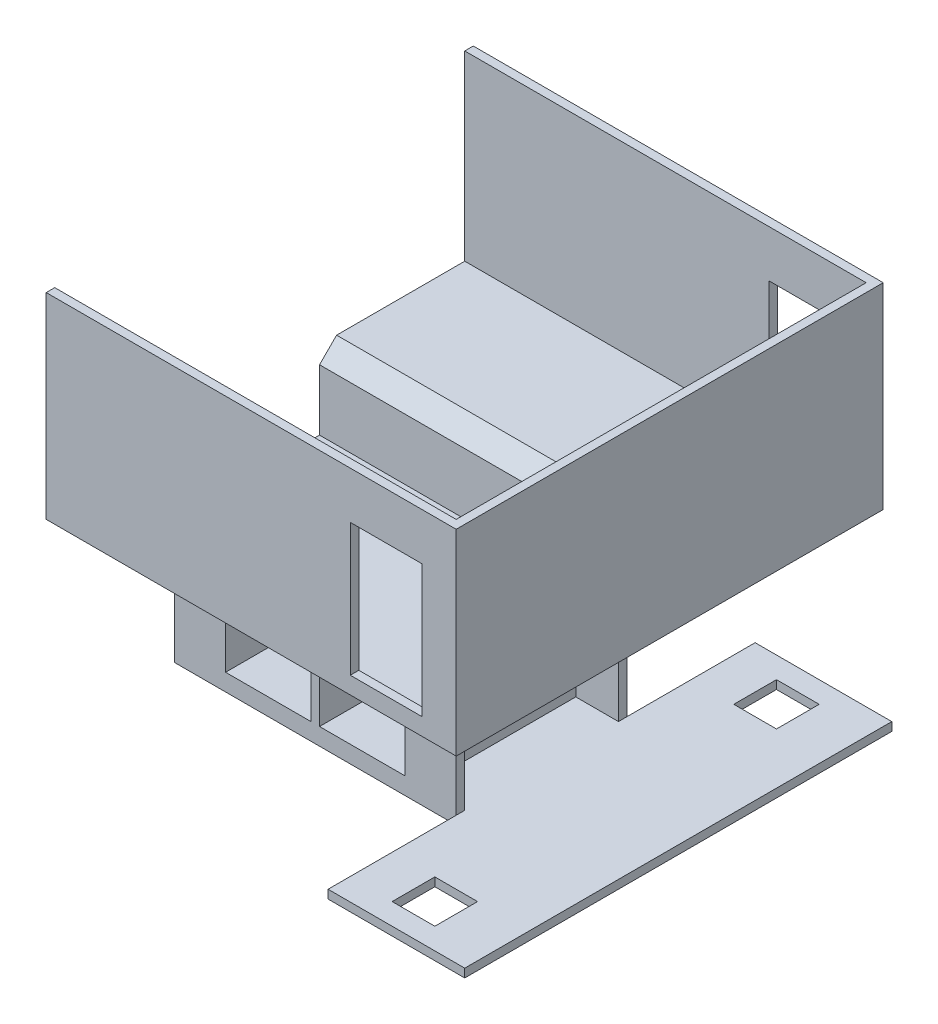
SolidWorks part; units mm, degrees
ref_plane "Front Plane" through (0, 0, 0) normal (0, 0, 1) x (1, 0, 0)
ref_plane "Top Plane" through (0, 0, 0) normal (0, 1, 0) x (1, 0, 0)
ref_plane "Right Plane" through (0, 0, 0) normal (1, 0, 0) x (0, 0, -1)
sketch "Sketch1" plane through (0, 0, 0) normal (0, 1, 0) x (1, 0, 0)
  line L1 (-23.6116, 30.0362) -> (21.3884, 30.0362)
  line L2 (-23.6116, 30.0362) -> (-23.6116, -19.9638)
  line L3 (-23.6116, -19.9638) -> (21.3884, -19.9638)
  line L4 (21.3884, 30.0362) -> (21.3884, -19.9638)
  dimension "D1" = 50
  dimension "D2" = 45
extrude "Boss-Extrude1" add sketch "Sketch1" along normal blind 45
sketch "Sketch2" plane through (0, 0, 19.9638) normal (0, 0, 1) x (1, 0, 0)
  line L1 (-23.6116, 0) -> (-1.6116, 0)
  line L2 (-23.6116, 0) -> (-23.6116, 22)
  line L3 (-23.6116, 22) -> (-1.6116, 22)
  line L4 (-1.6116, 0) -> (-1.6116, 22)
  dimension "D1" = 22
  dimension "D2" = 22
extrude "Cut-Extrude2" cut sketch "Sketch2" against normal blind 15
sketch "Sketch3" plane through (0, 0, 4.9638) normal (0, 0, 1) x (1, 0, 0)
  line L0 (-23.6116, 0) -> (-1.6116, 0) construction
  line L1 (-7.6116, 2) -> (-17.6116, 2)
  line L2 (-7.6116, 2) -> (-7.6116, 14)
  line L3 (-7.6116, 14) -> (-17.6116, 14)
  line L4 (-17.6116, 2) -> (-17.6116, 14)
  line L5 (-23.6116, 22) -> (-23.6116, 0) construction
  line L6 (-1.6116, 0) -> (-1.6116, 22) construction
  dimension "D1" = 10
  dimension "D2" = 12
  dimension "D3" = 2
  dimension "D4" = 6
  dimension "D5" = 6
extrude "Cut-Extrude3" cut sketch "Sketch3" against normal blind 70
sketch "Sketch4" plane through (0, 0, -30.0362) normal (0, 0, -1) x (-1, 0, 0)
  line L0 (7.6116, 2) -> (7.6116, 14) construction
  line L1 (6.6116, 2) -> (-3.3884, 2)
  line L2 (6.6116, 2) -> (6.6116, 14)
  line L3 (6.6116, 14) -> (-3.3884, 14)
  line L4 (-3.3884, 2) -> (-3.3884, 14)
  line L6 (-21.3884, 0) -> (23.6116, 0) construction
  dimension "D1" = 10
  dimension "D2" = 12
  dimension "D3" = 1
  dimension "D4" = 2
extrude "Cut-Extrude4" cut sketch "Sketch4" against normal blind 70
sketch "Sketch5" plane through (0, 0, -30.0362) normal (0, 0, -1) x (-1, 0, 0)
  line L0 (-21.3884, 0) -> (23.6116, 0) construction
  line L1 (-9.3884, 0) -> (12.6116, 0)
  line L2 (-9.3884, 0) -> (-9.3884, 22)
  line L3 (-9.3884, 22) -> (12.6116, 22)
  line L4 (12.6116, 0) -> (12.6116, 22)
  dimension "D1" = 22
  dimension "D2" = 22
  dimension "D3" = 6
  dimension "D4" = 6
extrude "Cut-Extrude5" cut sketch "Sketch5" against normal blind 15
sketch "Sketch6" plane through (-23.6116, 0, 0) normal (-1, 0, 0) x (0, 0, 1)
  line L1 (-30.0362, 0) -> (-15.0362, 0)
  line L2 (-30.0362, 0) -> (-30.0362, 21.8834)
  line L3 (-30.0362, 21.8834) -> (-15.0362, 21.8834)
  line L4 (-15.0362, 0) -> (-15.0362, 21.8834)
  dimension "D1" = 15
extrude "Cut-Extrude6" cut sketch "Sketch6" against normal blind 15
sketch "Sketch7" plane through (0, 0, 19.9638) normal (0, 0, 1) x (1, 0, 0)
  line L1 (-1.6116, 0) -> (3.3884, 0)
  line L2 (-1.6116, 0) -> (-1.6116, 22)
  line L3 (-1.6116, 22) -> (3.3884, 22)
  line L4 (3.3884, 0) -> (3.3884, 22)
  dimension "D1" = 22
extrude "Cut-Extrude7" cut sketch "Sketch7" against normal blind 15
sketch "Sketch8" plane through (-23.6116, 0, 0) normal (-1, 0, 0) x (0, 0, 1)
  line L0 (-30.0362, 45) -> (19.9638, 45) construction
  line L1 (-29.0362, 23.681) -> (18.9638, 23.681)
  line L2 (-29.0362, 23.681) -> (-29.0362, 45)
  line L3 (-29.0362, 45) -> (18.9638, 45)
  line L4 (18.9638, 23.681) -> (18.9638, 45)
  line L5 (-30.0362, 45) -> (-30.0362, 21.8834) construction
  line L6 (19.9638, 45) -> (19.9638, 22) construction
  dimension "D1" = 1
  dimension "D2" = 1
extrude "Cut-Extrude8" cut sketch "Sketch8" against normal blind 44
sketch "Sketch9" plane through (-12.6116, 0, 0) normal (1, 0, 0) x (0, 0, -1)
  line L1 (30.0362, 21.8834) -> (15.0362, 21.8834)
  line L2 (30.0362, 21.8834) -> (30.0362, 22)
  line L3 (30.0362, 22) -> (15.0362, 22)
  line L4 (15.0362, 21.8834) -> (15.0362, 22)
extrude "Cut-Extrude9" cut sketch "Sketch9" against normal blind 44
sketch "Sketch10" plane through (-23.6116, 0, 0) normal (-1, 0, 0) x (0, 0, 1)
  line L0 (-29.0362, 23.681) -> (18.9638, 23.681) construction
  line L1 (-14.0362, 14.5456) -> (3.9638, 14.5456)
  line L2 (-14.0362, 14.5456) -> (-14.0362, 23.681)
  line L3 (-14.0362, 23.681) -> (3.9638, 23.681)
  line L4 (3.9638, 14.5456) -> (3.9638, 23.681)
  line L5 (-15.0362, 0) -> (-15.0362, 22) construction
  line L6 (4.9638, 22) -> (4.9638, 0) construction
  dimension "D1" = 1
  dimension "D2" = 1
extrude "Cut-Extrude10" cut sketch "Sketch10" against normal blind 44
sketch "Sketch11" plane through (0, 0, -30.0362) normal (0, 0, -1) x (-1, 0, 0)
  line L1 (-9.3884, 0) -> (-21.3884, 0)
  line L2 (-9.3884, 0) -> (-9.3884, 45)
  line L3 (-9.3884, 45) -> (-21.3884, 45)
  line L4 (-21.3884, 0) -> (-21.3884, 45)
extrude "Cut-Extrude11" cut sketch "Sketch11" against normal blind 50
sketch "Sketch12" plane through (9.3884, 0, 0) normal (1, 0, 0) x (0, 0, -1)
  line L0 (-3.9638, 23.681) -> (-3.9638, 14.5456) construction
  line L1 (-19.9638, 0) -> (-4.9638, 0)
  line L2 (-19.9638, 0) -> (-19.9638, 22)
  line L3 (-19.9638, 22) -> (-4.9638, 22)
  line L4 (-4.9638, 0) -> (-4.9638, 22)
  dimension "D1" = 1
  dimension "D2" = 0
extrude "Cut-Extrude12" cut sketch "Sketch12" against normal blind 10
sketch "Sketch14" plane through (9.3884, 0, 0) normal (1, 0, 0) x (0, 0, -1)
  line L0 (-4.9638, 0) -> (15.0362, 0) construction
  line L1 (-3.9638, 14.5456) -> (14.0362, 14.5456)
  line L2 (-3.9638, 14.5456) -> (-3.9638, 1)
  line L3 (-3.9638, 1) -> (14.0362, 1)
  line L4 (14.0362, 14.5456) -> (14.0362, 1)
  line L5 (14.0362, 14.5456) -> (14.0362, 23.681) construction
  dimension "D1" = 1
  dimension "D2" = 0
extrude "Cut-Extrude17" cut sketch "Sketch14" against normal blind 5
sketch "Sketch16" plane through (0, 0, 0) normal (0, -1, 0) x (-1, 0, 0)
  line L2 (-9.3884, -4.9638) -> (-9.3884, 30.0362)
  line L3 (-9.3884, 30.0362) -> (-25.286, 30.0362)
  line L4 (-25.286, -1.1069) -> (-25.286, 30.0362)
  line L6 (-9.3884, -4.9638) -> (-9.3884, -19.9638)
  line L7 (-9.3884, -19.9638) -> (-25.286, -19.9638)
  line L8 (-25.286, -1.1069) -> (-25.286, -19.9638)
  dimension "D1" = 50
  dimension "D2" = 0
extrude "Boss-Extrude2" add sketch "Sketch16" against normal blind 1
sketch "Sketch18" plane through (0, 1, 0) normal (0, 1, 0) x (1, 0, 0)
  line L1 (9.3884, -19.9638) -> (25.3884, -19.9638)
  line L2 (9.3884, -19.9638) -> (9.3884, 30.0362)
  line L3 (9.3884, 30.0362) -> (25.3884, 30.0362)
  line L4 (25.3884, -19.9638) -> (25.3884, 30.0362)
  dimension "D1" = 16
extrude "Boss-Extrude3" add sketch "Sketch18" against normal blind 1
sketch "Sketch19" plane through (0, 1, 0) normal (0, 1, 0) x (1, 0, 0)
  line L0 (25.3884, -19.9638) -> (9.3884, -19.9638) construction
  line L1 (14.3884, -17.4638) -> (19.3884, -17.4638)
  line L2 (14.3884, -17.4638) -> (14.3884, -12.4638)
  line L3 (14.3884, -12.4638) -> (19.3884, -12.4638)
  line L4 (19.3884, -17.4638) -> (19.3884, -12.4638)
  line L5 (14.3884, 22.5362) -> (19.3884, 22.5362)
  line L6 (14.3884, 22.5362) -> (14.3884, 27.5362)
  line L7 (14.3884, 27.5362) -> (19.3884, 27.5362)
  line L8 (19.3884, 22.5362) -> (19.3884, 27.5362)
  line L9 (9.3884, 30.0362) -> (25.3884, 30.0362) construction
  line L10 (9.3884, -19.9638) -> (9.3884, -4.9638) construction
  line L11 (9.3884, 15.0362) -> (9.3884, 30.0362) construction
  dimension "D1" = 5
  dimension "D2" = 5
  dimension "D3" = 5
  dimension "D4" = 2.5
  dimension "D5" = 2.5
  dimension "D6" = 5
  dimension "D7" = 5
extrude "Cut-Extrude18" cut sketch "Sketch19" against normal blind 1
sketch "Sketch21" plane through (9.3884, 0, 0) normal (1, 0, 0) x (0, 0, -1)
  line L1 (-19.9638, 22) -> (30.0362, 22)
  line L2 (-19.9638, 22) -> (-19.9638, 45)
  line L3 (-19.9638, 45) -> (30.0362, 45)
  line L4 (30.0362, 22) -> (30.0362, 45)
extrude "Boss-Extrude4" add sketch "Sketch21" along normal blind 15
sketch "Sketch22" plane through (0, 0, 19.9638) normal (0, 0, 1) x (1, 0, 0)
  line L0 (24.3884, 22) -> (-23.6116, 22) construction
  line L1 (20.3884, 39.5) -> (11.9884, 39.5)
  line L2 (20.3884, 39.5) -> (20.3884, 24)
  line L3 (20.3884, 24) -> (11.9884, 24)
  line L4 (11.9884, 39.5) -> (11.9884, 24)
  line L5 (24.3884, 45) -> (24.3884, 22) construction
  dimension "D1" = 8.4
  dimension "D2" = 15.5
  dimension "D3" = 2
  dimension "D4" = 4
extrude "Cut-Extrude21" cut sketch "Sketch22" against normal blind 90
sketch "Sketch24" plane through (9.3884, 0, 0) normal (-1, 0, 0) x (0, 0, 1)
  line L1 (-29.0362, 23.681) -> (18.9638, 23.681)
  line L2 (-29.0362, 23.681) -> (-29.0362, 45)
  line L3 (-29.0362, 45) -> (18.9638, 45)
  line L4 (18.9638, 23.681) -> (18.9638, 45)
extrude "Cut-Extrude22" cut sketch "Sketch24" against normal blind 14
sketch "Sketch25" plane through (0, 14.5456, 0) normal (0, 1, 0) x (1, 0, 0)
  line L0 (-23.6116, 14.0362) -> (-23.6116, -3.9638) construction
  line L1 (4.3884, 14.0362) -> (-23.6116, 14.0362)
  line L2 (4.3884, 14.0362) -> (4.3884, 12.0362)
  line L3 (4.3884, 12.0362) -> (-23.6116, 12.0362)
  line L4 (-23.6116, 14.0362) -> (-23.6116, 12.0362)
  line L5 (4.3884, 14.0362) -> (4.3884, -3.9638) construction
  line L6 (4.3884, -1.9638) -> (-23.6116, -1.9638)
  line L7 (4.3884, -1.9638) -> (4.3884, -3.9638)
  line L8 (4.3884, -3.9638) -> (-23.6116, -3.9638)
  line L9 (-23.6116, -1.9638) -> (-23.6116, -3.9638)
  dimension "D1" = 2
  dimension "D2" = 2
extrude "Boss-Extrude5" add sketch "Sketch25" along normal blind 9.1353
chamfer "Chamfer1" distance 2 angle 45 2 edges at (-9.6116, 23.681, 1.9638) (-9.6116, 23.681, -12.0362)
sketch "Sketch26" plane through (24.3884, 0, 0) normal (1, 0, 0) x (0, 0, -1)
  line L0 (-18.9638, 45) -> (29.0362, 45) construction
  line L1 (23.5362, 39) -> (18.5362, 39)
  line L2 (23.5362, 39) -> (23.5362, 37)
  line L3 (23.5362, 37) -> (18.5362, 37)
  line L4 (18.5362, 39) -> (18.5362, 37)
  line L5 (-8.4638, 39) -> (-13.4638, 39)
  line L6 (-8.4638, 39) -> (-8.4638, 37)
  line L7 (-8.4638, 37) -> (-13.4638, 37)
  line L8 (-13.4638, 39) -> (-13.4638, 37)
  line L9 (29.0362, 45) -> (29.0362, 23.681) construction
  line L10 (-18.9638, 23.681) -> (-18.9638, 45) construction
  dimension "D1" = 27
  dimension "D2" = 6
  dimension "D3" = 6
  dimension "D4" = 5.5
  dimension "D5" = 5
  dimension "D6" = 5
  dimension "D7" = 2
  dimension "D8" = 2
  dimension "D9" = 5.5
extrude "Boss-Extrude7" add sketch "Sketch26" against normal blind 5
sketch "Sketch27" plane through (0, 39, 0) normal (0, 1, 0) x (1, 0, 0)
  line L0 (19.3884, -8.4638) -> (23.3884, -8.4638) construction
  line L1 (19.3884, -8.4638) -> (19.3884, -13.4638) construction
  line L2 (19.3884, 18.5362) -> (23.3884, 18.5362) construction
  circle A0 centre (21.1384, -10.9638) radius 1
  circle A1 centre (21.1384, 21.0362) radius 1
  point P2 (21.3884, -8.4638)
  point P9 (21.3884, 18.5362)
  dimension "D3" = 2.5
  dimension "D4" = 2
  dimension "D1" = 2.5
  dimension "D2" = 1.75
extrude "Cut-Extrude23" cut sketch "Sketch27" against normal blind 5
